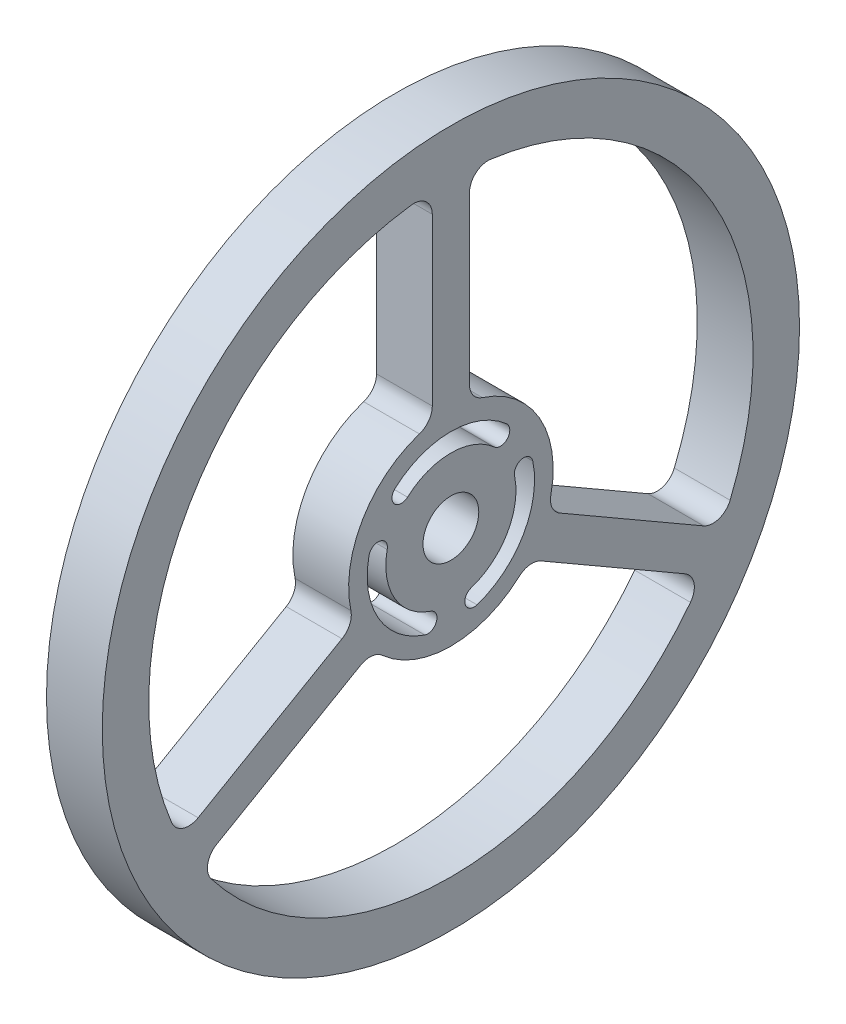
SolidWorks part; units mm, degrees
material "Acrylic (Medium-high impact)"
ref_plane "Front Plane" through (0, 0, 0) normal (0, 0, 1) x (1, 0, 0)
ref_plane "Top Plane" through (0, 0, 0) normal (0, 1, 0) x (1, 0, 0)
ref_plane "Right Plane" through (0, 0, 0) normal (1, 0, 0) x (0, 0, -1)
sketch "Sketch1" plane through (0, 0, 0) normal (1, 0, 0) x (0, 0, -1)
  line L0 (0, 0) -> (0, 37.5) construction
  line L1 (-2, 32.4384) -> (-2, 10.8167)
  line L2 (2, 32.4384) -> (2, 10.8167)
  line L3 (29.0925, -14.4872) -> (10.3675, -3.6763)
  line L4 (27.0925, -17.9513) -> (8.3675, -7.1404)
  line L5 (-27.0925, -17.9513) -> (-8.3675, -7.1404)
  line L6 (-29.0925, -14.4872) -> (-10.3675, -3.6763)
  circle A0 centre (0, 0) radius 37.5
  circle A2 centre (0, 0) radius 32.5
  circle A3 centre (0, 0) radius 3
  circle A4 centre (0, 0) radius 11
  point P23 (0, 0)
  dimension "D1" = 75
  dimension "D3" = 6
  dimension "D6" = 4
  dimension "D2" = 5
  dimension "D4" = 8
  dimension "D5" = 3
extrude "Boss-Extrude1" add sketch "Sketch1" along normal blind 6 contours A2 A0 | A3 A4 | A4 L6 A2 L5 | L0 A4 L2 A2 | A4 L0 A2 L1 | A4 L4 A2 L3 region at (0, 10.6442, -0.9758) region at (0, 21.7092, 1.0009) region at (0, 21.7092, -1.0009) region at (0, 25.7665, -25.7665) region at (0, -10.8546, 18.8007) region at (0, -10.8546, -18.8007)
fillet "Fillet1" radius 2 12 edges at (3, -3.6763, 10.3675) (3, -7.1404, 8.3675) (3, -7.1404, -8.3675) (3, -3.6763, -10.3675) (3, 10.8167, -2) (3, -17.9513, -27.0925) (3, -14.4872, -29.0925) (3, -17.9513, 27.0925) (3, -14.4872, 29.0925) (3, 32.4384, -2) (3, 32.4384, 2) (3, 10.8167, 2)
sketch "Sketch2" plane through (6, 0, 0) normal (1, 0, 0) x (0, 0, -1)
  line L0 (0, 0) -> (0, 11.7058) construction
  line L1 (4.6667, 5.2175) -> (6, 6.7082) construction
  arc A0 (0, 9) -> (6, 6.7082) centre (0, 0) cw
  arc A1 (0, 7) -> (4.6667, 5.2175) centre (0, 0) cw
  circle A2 centre (5.3333, 5.9628) radius 1
  circle A3 centre (-5.3333, 5.9628) radius 1
  arc A4 (0, 7) -> (-4.6667, 5.2175) centre (0, 0) ccw
  arc A5 (0, 9) -> (-6, 6.7082) centre (0, 0) ccw
  dimension "D1" = 9
  dimension "D2" = 6
  dimension "D3" = 2
extrude "Cut-Extrude1" cut sketch "Sketch2" against normal blind 10 contours A0 A5 A3 A4 A1 A2 | A3 | A2 region at (6, 7.5179, 0) region at (6, 5.9628, -5.3333) region at (6, 5.9628, 5.3333)
pattern_circular "CirPattern1" count 3 over 360 about axis through (6, 0, 0) along (1, 0, 0) of "Cut-Extrude1"
